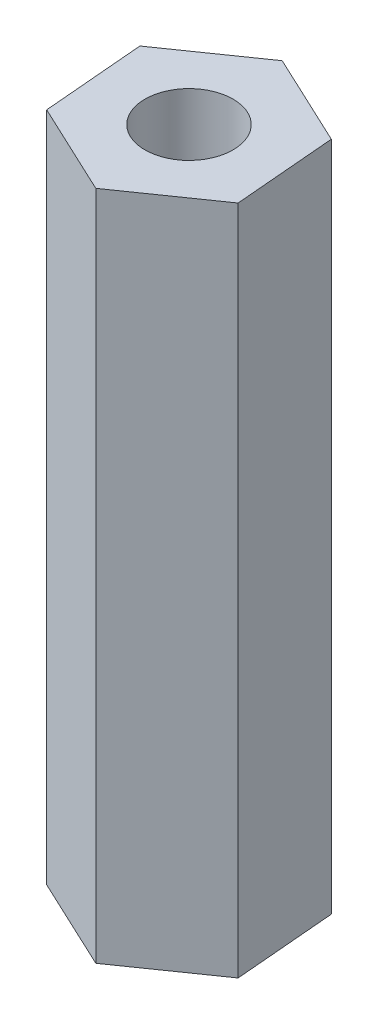
SolidWorks part; units mm, degrees
material "Brass"
ref_plane "Front" through (0, 0, 0) normal (0, 0, 1) x (1, 0, 0)
ref_plane "Top" through (0, 0, 0) normal (0, 1, 0) x (1, 0, 0)
ref_plane "Right" through (0, 0, 0) normal (1, 0, 0) x (0, 0, -1)
ref_axis "Axis1" through (0, 0, 55) along (0, 0, -1)
sketch "Sketch1" plane through (0, 0, 0) normal (0, 1, 0) x (1, 0, 0)
  line L1 (2.6267, -1.2329) -> (2.3811, 1.6583)
  line L2 (2.3811, 1.6583) -> (-0.2456, 2.8912)
  line L3 (-0.2456, 2.8912) -> (-2.6267, 1.2329)
  line L4 (-2.6267, 1.2329) -> (-2.3811, -1.6583)
  line L5 (-2.3811, -1.6583) -> (0.2456, -2.8912)
  line L6 (0.2456, -2.8912) -> (2.6267, -1.2329)
  circle A0 centre (0, 0) radius 2.5129 construction
  circle A1 centre (0, 0) radius 1.25
  dimension "D1" = 2.5
  dimension "D2" = 5.0258
  dimension "D3" = 0.2456
extrude "Boss-Extrude1" add sketch "Sketch1" along normal blind 19.05
